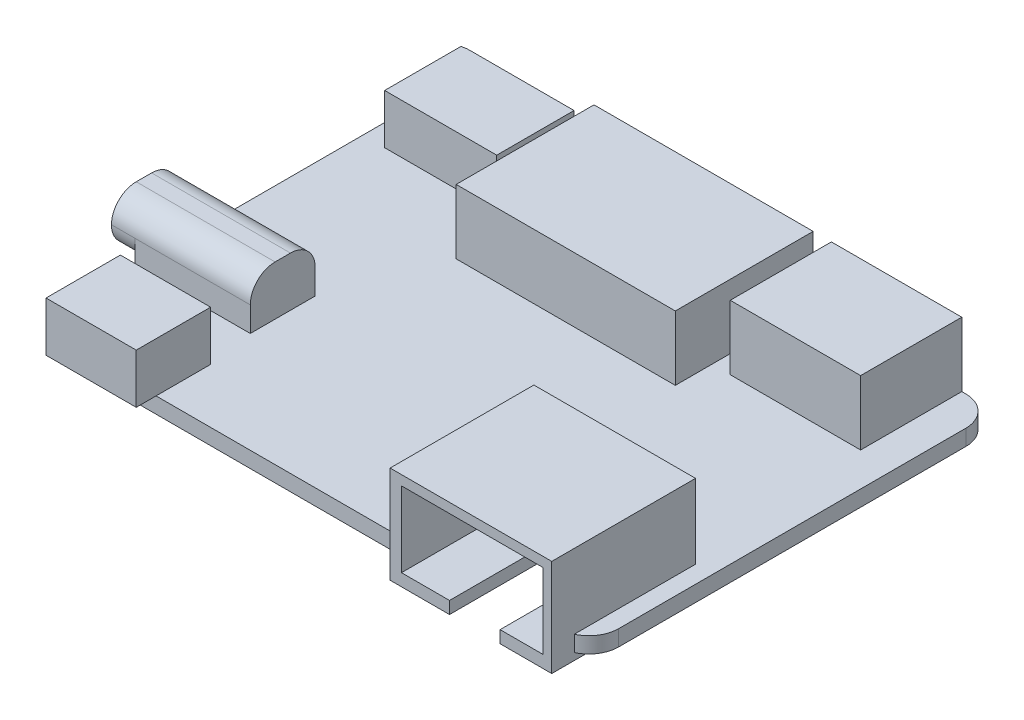
SolidWorks part; units mm, degrees
ref_plane "Front Plane" through (0, 0, 0) normal (0, 0, 1) x (1, 0, 0)
ref_plane "Top Plane" through (0, 0, 0) normal (0, 1, 0) x (1, 0, 0)
ref_plane "Right Plane" through (0, 0, 0) normal (1, 0, 0) x (0, 0, -1)
sketch "Sketch1" plane through (0, 0, 0) normal (0, 1, 0) x (1, 0, 0)
  line L1 (3, 0) -> (53, 0)
  line L2 (0, 3) -> (0, 38)
  line L3 (3, 41) -> (53, 41)
  line L4 (56, 3) -> (56, 38)
  line L5 (54.25, 12.5) -> (37.95, 12.5)
  line L6 (54.25, 12.5) -> (54.25, -2)
  line L7 (54.25, -2) -> (37.95, -2)
  line L8 (37.95, 12.5) -> (37.95, -2)
  line L9 (3.25, 5.5) -> (12.35, 5.5)
  line L10 (3.25, 5.5) -> (3.25, -2)
  line L11 (3.25, -2) -> (12.35, -2)
  line L12 (12.35, 5.5) -> (12.35, -2)
  line L13 (-2.35, 16.75) -> (11.65, 16.75)
  line L14 (-2.35, 16.75) -> (-2.35, 10.2)
  line L15 (-2.35, 10.2) -> (11.65, 10.2)
  line L16 (11.65, 16.75) -> (11.65, 10.2)
  line L21 (2.2, 41) -> (13.5, 41)
  line L22 (2.2, 41) -> (2.2, 33.2)
  line L23 (2.2, 33.2) -> (13.5, 33.2)
  line L24 (13.5, 41) -> (13.5, 33.2)
  line L25 (52.6, 41) -> (39.45, 41)
  line L26 (52.6, 41) -> (52.6, 30.8)
  line L27 (52.6, 30.8) -> (39.45, 30.8)
  line L28 (39.45, 41) -> (39.45, 30.8)
  line L29 (15.5115, 41) -> (37.6115, 41)
  line L30 (15.5115, 41) -> (15.5115, 27.1)
  line L31 (15.5115, 27.1) -> (37.6115, 27.1)
  line L32 (37.6115, 41) -> (37.6115, 27.1)
  arc A0 (53, 41) -> (56, 38) centre (53, 38) cw
  arc A1 (53, 0) -> (56, 3) centre (53, 3) ccw
  arc A2 (3, 0) -> (0, 3) centre (3, 3) cw
  arc A3 (0, 38) -> (3, 41) centre (3, 38) cw
  point P7 (56, 41)
  point P10 (56, 0)
  point P13 (0, 0)
  point P28 (15.5115, 27.1)
  point P29 (39.45, 28.9203)
  point P30 (13.5, 30.3355)
  point P40 (15.4779, 26.364)
  point P41 (0, 0)
  dimension "D3" = 3
  dimension "D1" = 56
  dimension "D2" = 41
  dimension "D4" = 16.3
  dimension "D5" = 13.15
  dimension "D6" = 11.3
  dimension "D7" = 9.1
  dimension "D8" = 2
  dimension "D9" = 1.75
  dimension "D10" = 3.25
  dimension "D11" = 2.2
  dimension "D12" = 3.4
  dimension "D13" = 6.55
  dimension "D14" = 10.2
  dimension "D15" = 2.35
  dimension "D16" = 22.1
  dimension "D17" = 13.9
  dimension "D18" = 14
  dimension "D19" = 14.5
  dimension "D20" = 7.5
  dimension "D21" = 10.2
  dimension "D22" = 7.8
extrude "Boss-Extrude1" add sketch "Sketch1" along normal blind 1.6 contours A3 L2 L13 L16 L15 A2 L10 L9 L12 L1 L8 L5 L6 A1 L4 A0 L26 L27 L28 L3 L24 L23 L22 | L16 L13 L2 L15 | L12 L9 L10 L1 | L2 | A3 L22 L23 L24 L3 | A0 L3 L28 L27 L26 | L1 A1 L6 L5 L8 | L32 L3 L30 L31 region at (27.1725, 0, -18.145) region at (7.8, 0, -2.75) region at (5.825, 0, -13.475) region at (46.0957, 0, -6.2534) region at (7.8518, 0, -37.0987) region at (26.5615, 0, -34.05) region at (46.025, 0, -35.9)
extrude "Boss-Extrude2" add sketch "Sketch1<3>" along normal blind 9.1 and the other way blind 0.7 contours L1 A1 L6 L5 L8 | A1 L1 L8 L7 L6 region at (46.0957, 0, -6.2534) region at (46.1267, 0, 0.9963)
sketch "Sketch1<3>" plane through (0, 0, 0) normal (0, 1, 0) x (1, 0, 0) same geometry as "Sketch1"
extrude "Boss-Extrude3" add sketch "Sketch1<4>" along normal blind 6.5 from surface contours L3 L28 L27 L26 | L32 L3 L30 L31 region at (26.5615, 0, -34.05) region at (46.025, 0, -35.9) starting at face at (32.289, 1.6, -17.2398)
sketch "Sketch1<4>" plane through (0, 0, 0) normal (0, 1, 0) x (1, 0, 0) same geometry as "Sketch1"
extrude "Boss-Extrude4" add sketch "Sketch1<5>" along normal blind 5 from surface contours L12 L1 L10 L11 | L12 L9 L10 L1 | L16 L13 L2 L15 | A3 L22 L23 L24 L3 | L14 L15 L16 L13 region at (7.8, 0, -2.75) region at (7.8, 0, 1) region at (5.825, 0, -13.475) region at (7.8518, 0, -37.0987) starting at face at (33.975, 1.6, -24.7072)
sketch "Sketch1<5>" plane through (0, 0, 0) normal (0, 1, 0) x (1, 0, 0) same geometry as "Sketch1"
sketch "Sketch2" plane through (0, 0, -41) normal (0, 0, -1) x (-1, 0, 0)
  line L1 (-51.465, 6.7819) -> (-40.4997, 6.7819)
  line L2 (-51.465, 6.7819) -> (-51.465, 4.9969)
  line L3 (-51.465, 4.9969) -> (-40.4997, 4.9969)
  line L4 (-40.4997, 6.7819) -> (-40.4997, 4.9969)
extrude "Cut-Extrude1" cut sketch "Sketch2" against normal blind 9
sketch "Sketch3" plane through (0, 0, 2) normal (0, 0, 1) x (1, 0, 0)
  line L0 (54.25, -0.7) -> (37.95, -0.7) construction
  line L1 (39.0972, 8.1207) -> (53.3776, 8.1207)
  line L2 (39.0972, 8.1207) -> (39.0972, 0.5343)
  line L3 (39.0972, 0.5343) -> (53.3776, 0.5343)
  line L4 (53.3776, 8.1207) -> (53.3776, 0.5343)
  line L5 (43.9423, 0.5343) -> (49.0425, 0.5343)
  line L6 (43.9423, 0.5343) -> (43.9423, -0.7)
  line L7 (43.9423, -0.7) -> (49.0425, -0.7)
  line L8 (49.0425, 0.5343) -> (49.0425, -0.7)
  line M12 (37.95, -0.7) -> (54.25, -0.7)
extrude "Cut-Extrude2" cut sketch "Sketch3" against normal blind 12 contours L8 L3 L6 M12 | L4 L1 L2 L3 | L2 L1 L4 L3 region at (46.2374, 4.3275, 2) region at (46.4924, -0.0829, 2)
fillet "Fillet1" radius 2.5 4 edges at (-1.175, 1.6, -16.75) (-1.175, 1.6, -10.2) (4.65, 6.6, -16.75) (4.65, 6.6, -10.2)
